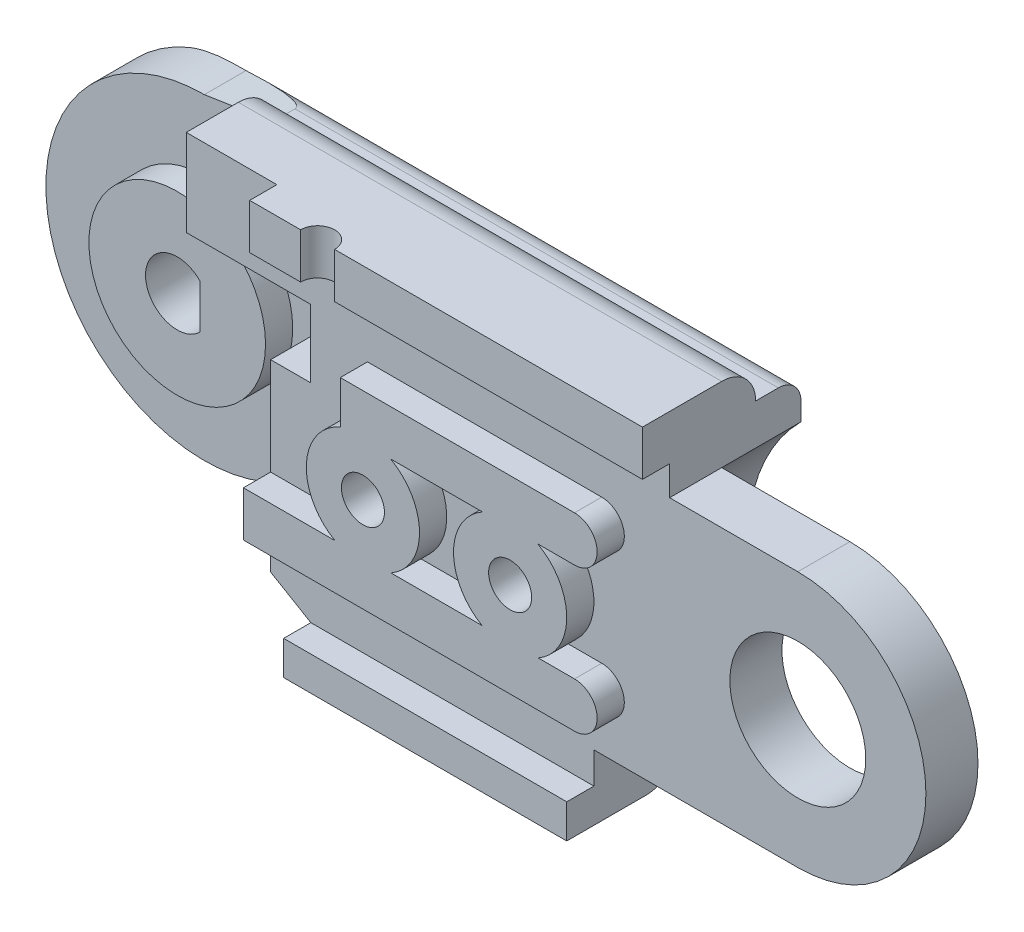
SolidWorks part; units mm, degrees
ref_plane "Front Plane" through (0, 0, 0) normal (0, 0, 1) x (1, 0, 0)
ref_plane "Top Plane" through (0, 0, 0) normal (0, 1, 0) x (1, 0, 0)
ref_plane "Right Plane" through (0, 0, 0) normal (1, 0, 0) x (0, 0, -1)
sketch "Sketch2" plane through (0, 0, 0) normal (0, 0, 1) x (1, 0, 0)
  line L0 (0, 0) -> (30, 0) construction
  line L1 (0, 19.5448) -> (0, -26.0212) construction
  line L2 (0, 7) -> (3, 7.4569)
  line L3 (3, 7.4569) -> (24.3431, 7.4569)
  line L4 (24.3431, 5.6569) -> (24.3431, 7.4569)
  line L5 (24.3431, 5.6569) -> (30, 0) construction
  line L6 (22, 0) -> (21, -2.5431)
  line L7 (21, -2.5431) -> (21, -7.0431)
  line L8 (21, -7.0431) -> (8.4997, -7.0431)
  line L9 (0, 0) -> (4.9497, -4.9497) construction
  line L10 (4.9497, -4.9497) -> (8.4997, -7.0431)
  arc A0 (0, 7) -> (4.9497, -4.9497) centre (0, 0) ccw
  arc A2 (24.3431, 5.6569) -> (22, 0) centre (30, 0) ccw
  dimension "D1" = 3
  dimension "D2" = 14
  dimension "D5" = 45
  dimension "D6" = 16
  dimension "D3" = 1.8
  dimension "D4" = 30
  dimension "D7" = 1
  dimension "D8" = 4.5
  dimension "D9" = 45
  dimension "D10" = 3.55
  dimension "D11" = 14.5
extrude "Boss-Extrude1" add sketch "Sketch2" along normal blind 2
sketch "Sketch3" plane through (0, 0, 2) normal (0, 0, 1) x (1, 0, 0)
  line L0 (24.3431, 7.4569) -> (24.3431, 5.6569)
  line L1 (22, 0) -> (21, -2.5431)
  line L2 (21, -2.5431) -> (22, 0) construction
  line L3 (21, -2.5431) -> (21, -7.0431)
  line L5 (8.4997, -7.0431) -> (6.7247, -5.9964)
  line L6 (4.9497, -4.9497) -> (8.4997, -7.0431) construction
  line L8 (3, 7.4569) -> (3, 2.1269)
  line L9 (3, 2.1269) -> (6.7247, 2.1269)
  line L10 (6.7247, 2.1269) -> (6.7247, -5.9964)
  line L11 (3, 7.4569) -> (3, 8.9569)
  line L12 (3, 8.9569) -> (24.3431, 8.9569)
  line L13 (24.3431, 8.9569) -> (24.3431, 7.4569)
  line L14 (8.4997, -7.0431) -> (8.4997, -8.5431)
  line L15 (8.4997, -8.5431) -> (21, -8.5431)
  line L16 (21, -8.5431) -> (21, -7.0431)
  line L17 (24.3431, 7.4569) -> (3, 7.4569) construction
  arc A0 (24.3431, 5.6569) -> (22, 0) centre (30, 0) ccw
  arc A1 (24.3431, 5.6569) -> (22, 0) centre (30, 0) ccw construction
  dimension "D1" = 5.33
  dimension "D2" = 1.5
  dimension "D3" = 1.5
extrude "Boss-Extrude2" add sketch "Sketch3" along normal blind 1.5
ref_plane "Plane1" through (0, 0, 3.5) normal (0, 0, 1) x (1, 0, 0)
sketch "Sketch5" plane through (0, 0, 3.5) normal (0, 0, 1) x (1, 0, 0)
  line L0 (3, 7.5) -> (3, 2.1269)
  line L1 (3, 2.1269) -> (6.7247, 2.1269)
  line L2 (6.7247, 2.1269) -> (6.7247, -5.9964)
  line L4 (8.4997, -8.5431) -> (21, -8.5431)
  line L6 (24.3431, 7.5) -> (24.3431, 5.6569)
  line L7 (24.3431, 5.6569) -> (30.0031, 5.6569)
  line L8 (30.0031, -5.6569) -> (21, -5.6569)
  line L9 (21, -8.5431) -> (21, -2.5431) construction
  line L10 (21, -5.6569) -> (21, -8.5431)
  line L11 (3, 7.5) -> (3, 8.9569)
  line L12 (3, 8.9569) -> (24.3431, 8.9569)
  line L13 (24.3431, 8.9569) -> (24.3431, 7.5)
  line L14 (6.7247, -5.9964) -> (8.4997, -7.0431)
  line L15 (8.4997, -7.0431) -> (8.4997, -8.5431)
  arc A0 (30.0031, -5.6569) -> (30.0031, 5.6569) centre (30.0031, 0) ccw
  dimension "D1" = 5.66
extrude "Boss-Extrude3" add sketch "Sketch5" along normal blind 2.3 contours A0 L7 L6 L13 L12 L11 L0 L1 L2 L14 L15 L4 L10 L8
sketch "Sketch6" plane through (0, 0, 5.8) normal (0, 0, 1) x (1, 0, 0)
  line L0 (3, 2.1269) -> (3, 5.1269)
  line L1 (3, 2.1269) -> (8.48, 2.1269)
  line L2 (3, 5.1269) -> (8.48, 5.1269)
  line L3 (8.48, 2.1269) -> (8.48, 5.1269)
  line L4 (3, 8.9569) -> (3, 2.1269) construction
  dimension "D1" = 3
  dimension "D2" = 5.48
extrude "Cut-Extrude1" cut sketch "Sketch6" against normal blind 3.8
sketch "Sketch7" plane through (0, 0, 5.8) normal (0, 0, 1) x (1, 0, 0)
  circle A0 centre (30.0031, 0) radius 3
  dimension "D1" = 6
extrude "Cut-Extrude2" cut sketch "Sketch7" against normal blind 3.3
sketch "Sketch8" plane through (0, 0, 5.8) normal (0, 0, 1) x (1, 0, 0)
  line L0 (24.3431, 8.9569) -> (7, 8.9569)
  line L1 (8.4997, -8.5431) -> (21, -8.5431) construction
  line L2 (7, 8.9569) -> (7, 6.9569)
  line L3 (7, 6.9569) -> (24.3431, 6.9569)
  line L4 (24.3431, 8.9569) -> (24.3431, 5.6569) construction
  line L5 (24.3431, 6.9569) -> (24.3431, 8.9569)
  line L6 (21, -8.5431) -> (21, -7.0431)
  line L7 (21, -8.5431) -> (8.4997, -8.5431)
  line L8 (8.4997, -8.5431) -> (8.4997, -7.0431)
  line L9 (8.4997, -7.0431) -> (21, -7.0431)
  line L10 (6.7247, -4.1721) -> (21.3431, -4.1721)
  line L11 (6.7247, 2.1269) -> (6.7247, -5.9964) construction
  line L12 (6.7247, -2.1721) -> (6.7247, -4.1721)
  line L13 (3, 8.9569) -> (24.3431, 8.9569) construction
  line L15 (21.3431, -2.1721) -> (6.7247, -2.1721)
  line L16 (21.3431, 4.1803) -> (11, 4.1803)
  line L17 (11, 4.1803) -> (11, 2.1803)
  line L18 (11, 2.1803) -> (21.3431, 2.1803)
  line L19 (3, 8.9569) -> (3, 5.1269) construction
  arc A0 (21.3431, -4.1721) -> (21.3431, -2.1721) centre (21.3431, -3.1721) ccw
  arc A1 (21.3431, 2.1803) -> (21.3431, 4.1803) centre (21.3431, 3.1803) ccw
  point P2 (11, 3.1803)
  dimension "D2" = 1
  dimension "D5" = 3
  dimension "D7" = 1
  dimension "D3" = 2
  dimension "D4" = 2
  dimension "D6" = 3
  dimension "D8" = 4.3524
  dimension "D9" = 4
  dimension "D10" = 2
  dimension "D11" = 4
extrude "Boss-Extrude4" add sketch "Sketch8" along normal blind 1.2
sketch "Sketch9" plane through (0, 0, 5.8) normal (0, 0, 1) x (1, 0, 0)
  line L0 (21, -8.5431) -> (21, -7.0431) construction
  circle A0 centre (18.5, 0) radius 2.5
  circle A1 centre (12, 0) radius 2.5
  dimension "D3" = 5
  dimension "D4" = 5
  dimension "D1" = 6.5
  dimension "D2" = 2.5
extrude "Boss-Extrude5" add sketch "Sketch9" along normal blind 1.2
sketch "Sketch10" plane through (0, 0, 7) normal (0, 0, 1) x (1, 0, 0)
  circle A0 centre (18.5, 0) radius 0.95
  circle A1 centre (12, 0) radius 0.95
extrude "Cut-Extrude3" cut sketch "Sketch10" against normal blind 8.2
sketch "Sketch11" plane through (0, 0, 0) normal (0, 0, -1) x (-1, 0, 0)
  circle A0 centre (-12, 0) radius 2
  circle A1 centre (-18.5, 0) radius 2
extrude "Cut-Extrude4" cut sketch "Sketch11" against normal blind 2.2
sketch "Sketch12" plane through (0, 0, 2) normal (0, 0, 1) x (1, 0, 0)
  circle A0 centre (0, 0) radius 3.9
extrude "Boss-Extrude6" add sketch "Sketch12" along normal blind 1.2
sketch "Sketch14" plane through (0, 0, 3.2) normal (0, 0, 1) x (1, 0, 0)
  line L0 (1, 0.9798) -> (1, -0.9798)
  arc A0 (1, 0.9798) -> (1, -0.9798) centre (0, 0) ccw
  dimension "D1" = 2.8
  dimension "D2" = 1
extrude "Cut-Extrude5" cut sketch "Sketch14" against normal blind 3.2 contours A0 L0
fillet "Fillet1" radius 1.5 2 edges at (13.6716, 8.9569, 2) (14.7499, -8.5431, 2)
fillet "Fillet2" radius 1 2 edges at (14.7499, -7.0431, 0) (13.6716, 7.4569, 0)
sketch "Sketch15" plane through (0, 6.9569, 0) normal (0, -1, 0) x (1, 0, 0)
  line L0 (7, 7) -> (24.3431, 7) construction
  line L1 (7, 7) -> (7, 5.8) construction
  circle A0 centre (10, 7) radius 0.75
  dimension "D1" = 3
extrude "Cut-Extrude6" cut sketch "Sketch15" against normal blind 4
